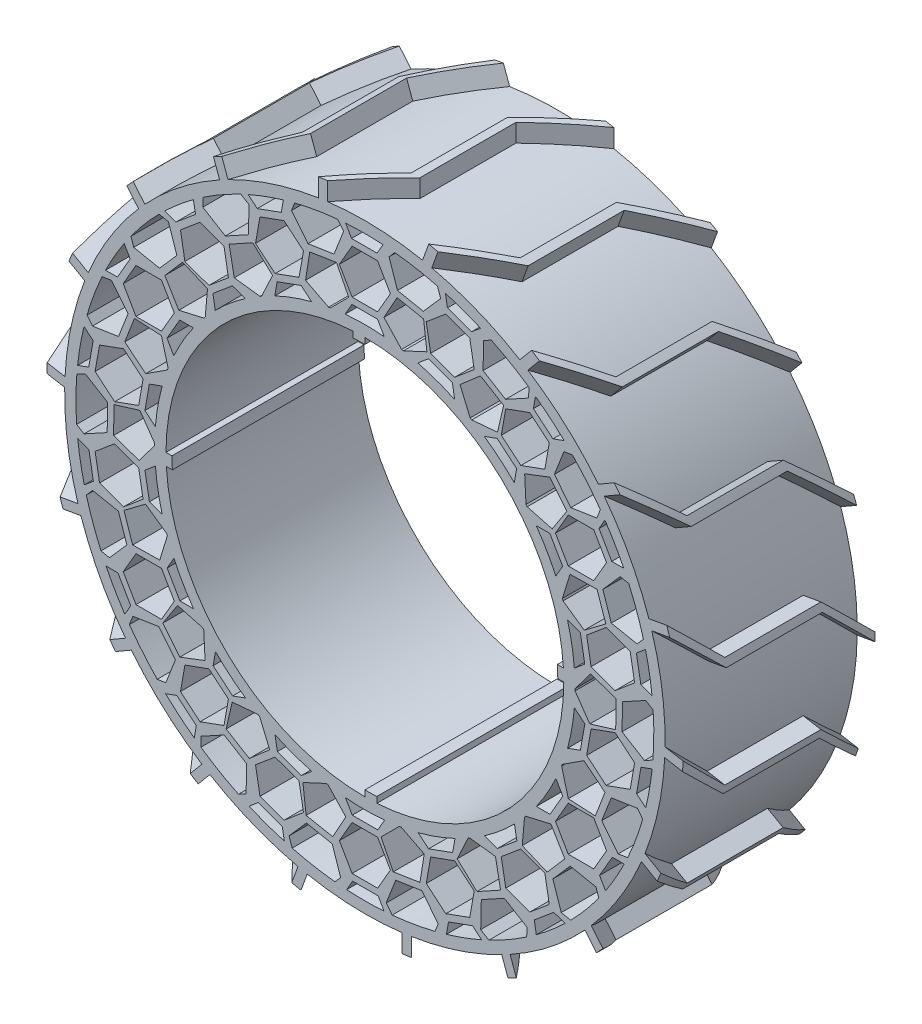
SolidWorks part; units mm, degrees
material "POLYURETHANE (11671)"
ref_plane "Front Plane" through (0, 0, 0) normal (0, 0, 1) x (1, 0, 0)
ref_plane "Top Plane" through (0, 0, 0) normal (0, 1, 0) x (1, 0, 0)
ref_plane "Right Plane" through (0, 0, 0) normal (1, 0, 0) x (0, 0, -1)
sketch "Sketch1" plane through (0, 0, 0) normal (0, 0, 1) x (1, 0, 0)
  line L0 (0, 120.3125) -> (0, 87.5) construction
  line L1 (5.083, 115.764) -> (7.5714, 120.074)
  line L2 (5.3125, 94.7047) -> (10.625, 103.9063)
  line L3 (10.625, 103.9063) -> (5.3125, 113.1078)
  line L4 (5.3125, 113.1078) -> (-5.3125, 113.1078)
  line L5 (-5.3125, 113.1078) -> (-10.625, 103.9062)
  line L6 (-10.625, 103.9062) -> (-5.3125, 94.7047)
  line L7 (-5.3125, 94.7047) -> (5.3125, 94.7047)
  line L12 (-5.542, 115.764) -> (5.083, 115.764)
  line L14 (8.0962, 87.1246) -> (5.2534, 92.0485)
  line L15 (5.2534, 92.0485) -> (-5.3716, 92.0485)
  line L16 (-5.3716, 92.0485) -> (-8.2212, 87.1129)
  line L19 (44.3701, 107.0441) -> (48.1825, 110.2431)
  line L20 (37.383, 87.1764) -> (45.5223, 94.006)
  line L21 (45.5223, 94.006) -> (43.6773, 104.4696)
  line L22 (43.6773, 104.4696) -> (33.693, 108.1035)
  line L23 (33.693, 108.1035) -> (25.5538, 101.2739)
  line L24 (25.5538, 101.2739) -> (27.3988, 90.8103)
  line L25 (27.3988, 90.8103) -> (37.383, 87.1764)
  line L27 (34.3859, 110.6781) -> (44.3701, 107.0441)
  line L28 (37.4063, 79.1013) -> (36.419, 84.7005)
  line L29 (36.419, 84.7005) -> (26.4348, 88.3345)
  line L30 (26.4348, 88.3345) -> (22.069, 84.6712)
  line L31 (41.1493, 113.0568) -> (29.9268, 82.2231) construction
  line L32 (78.3055, 85.4131) -> (82.9821, 87.1152)
  line L33 (64.9446, 69.1332) -> (74.9289, 72.7672)
  line L34 (74.9289, 72.7672) -> (76.7739, 83.2308)
  line L35 (76.7739, 83.2308) -> (68.6347, 90.0604)
  line L36 (68.6347, 90.0604) -> (58.6504, 86.4264)
  line L37 (58.6504, 86.4264) -> (56.8054, 75.9628)
  line L38 (56.8054, 75.9628) -> (64.9446, 69.1332)
  line L40 (70.1663, 92.2427) -> (78.3055, 85.4131)
  line L41 (62.2047, 61.5372) -> (63.192, 67.1364)
  line L42 (63.192, 67.1364) -> (55.0527, 73.966)
  line L43 (55.0527, 73.966) -> (49.6973, 72.0168)
  line L44 (77.3354, 92.1647) -> (56.2439, 67.0289) construction
  line L45 (102.7961, 53.48) -> (107.7729, 53.48)
  line L46 (84.673, 42.7516) -> (95.298, 42.7516)
  line L47 (95.298, 42.7516) -> (100.6105, 51.9531)
  line L48 (100.6105, 51.9531) -> (95.298, 61.1546)
  line L49 (95.298, 61.1546) -> (84.673, 61.1546)
  line L50 (84.673, 61.1546) -> (79.3605, 51.9531)
  line L51 (79.3605, 51.9531) -> (84.673, 42.7516)
  line L53 (97.4836, 62.6815) -> (102.7961, 53.48)
  line L54 (79.5002, 36.5508) -> (82.343, 41.4747)
  line L55 (82.343, 41.4747) -> (77.0305, 50.6762)
  line L56 (77.0305, 50.6762) -> (71.3314, 50.6762)
  line L57 (104.1937, 60.1563) -> (75.7772, 43.75) construction
  line L58 (114.888, 15.0964) -> (119.5646, 13.3942)
  line L59 (94.1885, 11.2135) -> (104.1727, 7.5795)
  line L60 (104.1727, 7.5795) -> (112.3119, 14.4092)
  line L61 (112.3119, 14.4092) -> (110.4669, 24.8727)
  line L62 (110.4669, 24.8727) -> (100.4827, 28.5067)
  line L63 (100.4827, 28.5067) -> (92.3434, 21.6771)
  line L64 (92.3434, 21.6771) -> (94.1885, 11.2135)
  line L66 (113.043, 25.56) -> (114.888, 15.0964)
  line L67 (87.2069, 7.1559) -> (91.5623, 10.8105)
  line L68 (91.5623, 10.8105) -> (89.7173, 21.2741)
  line L69 (89.7173, 21.2741) -> (84.3619, 23.2233)
  line L70 (118.4847, 20.892) -> (86.1707, 15.1942) construction
  line L71 (113.1226, -25.108) -> (116.9351, -28.307)
  line L72 (92.3434, -21.6771) -> (100.4827, -28.5067)
  line L73 (100.4827, -28.5067) -> (110.4669, -24.8727)
  line L74 (110.4669, -24.8727) -> (112.3119, -14.4092)
  line L75 (112.3119, -14.4092) -> (104.1727, -7.5795)
  line L76 (104.1727, -7.5795) -> (94.1885, -11.2135)
  line L77 (94.1885, -11.2135) -> (92.3434, -21.6771)
  line L79 (114.9677, -14.6444) -> (113.1226, -25.108)
  line L80 (84.3951, -23.1022) -> (89.7378, -21.1576)
  line L81 (89.7378, -21.1576) -> (91.5828, -10.694)
  line L82 (91.5828, -10.694) -> (87.2171, -7.0307)
  line L83 (118.4847, -20.892) -> (86.1707, -15.1942) construction
  line L84 (97.7131, -62.284) -> (100.2014, -66.594)
  line L85 (79.3605, -51.9531) -> (84.673, -61.1546)
  line L86 (84.673, -61.1546) -> (95.298, -61.1546)
  line L87 (95.298, -61.1546) -> (100.6105, -51.9531)
  line L88 (100.6105, -51.9531) -> (95.298, -42.7516)
  line L89 (95.298, -42.7516) -> (84.673, -42.7516)
  line L90 (84.673, -42.7516) -> (79.3605, -51.9531)
  line L92 (103.0256, -53.0825) -> (97.7131, -62.284)
  line L93 (71.4041, -50.5738) -> (77.0896, -50.5738)
  line L94 (77.0896, -50.5738) -> (82.4021, -41.3723)
  line L95 (82.4021, -41.3723) -> (79.5526, -36.4367)
  line L96 (104.1937, -60.1563) -> (75.7772, -43.75) construction
  line L97 (70.5178, -91.9477) -> (71.3821, -96.8489)
  line L98 (56.8054, -75.9628) -> (58.6504, -86.4264)
  line L99 (58.6504, -86.4264) -> (68.6347, -90.0604)
  line L100 (68.6347, -90.0604) -> (76.7739, -83.2308)
  line L101 (76.7739, -83.2308) -> (74.9289, -72.7672)
  line L102 (74.9289, -72.7672) -> (64.9446, -69.1332)
  line L103 (64.9446, -69.1332) -> (56.8054, -75.9628)
  line L105 (78.6571, -85.1181) -> (70.5178, -91.9477)
  line L106 (49.8006, -71.9455) -> (55.1433, -73.89)
  line L107 (55.1433, -73.89) -> (63.2825, -67.0604)
  line L108 (63.2825, -67.0604) -> (62.2929, -61.4479)
  line L109 (77.3354, -92.1647) -> (56.2439, -67.0289) construction
  line L110 (34.8171, -110.5211) -> (33.9529, -115.4223)
  line L111 (27.3988, -90.8103) -> (25.5538, -101.2739)
  line L112 (25.5538, -101.2739) -> (33.693, -108.1035)
  line L113 (33.693, -108.1035) -> (43.6773, -104.4696)
  line L114 (43.6773, -104.4696) -> (45.5223, -94.006)
  line L115 (45.5223, -94.006) -> (37.383, -87.1764)
  line L116 (37.383, -87.1764) -> (27.3988, -90.8103)
  line L118 (44.8014, -106.8871) -> (34.8171, -110.5211)
  line L119 (22.1905, -84.6394) -> (26.5459, -88.294)
  line L120 (26.5459, -88.294) -> (36.5301, -84.6601)
  line L121 (36.5301, -84.6601) -> (37.5197, -79.0476)
  line L122 (41.1493, -113.0568) -> (29.9268, -82.2231) construction
  line L123 (-5.083, -115.764) -> (-7.5714, -120.074)
  line L124 (-5.3125, -94.7047) -> (-10.625, -103.9063)
  line L125 (-10.625, -103.9063) -> (-5.3125, -113.1078)
  line L126 (-5.3125, -113.1078) -> (5.3125, -113.1078)
  line L127 (5.3125, -113.1078) -> (10.625, -103.9063)
  line L128 (10.625, -103.9063) -> (5.3125, -94.7047)
  line L129 (5.3125, -94.7047) -> (-5.3125, -94.7047)
  line L131 (5.542, -115.764) -> (-5.083, -115.764)
  line L132 (-8.0962, -87.1246) -> (-5.2534, -92.0485)
  line L133 (-5.2534, -92.0485) -> (5.3716, -92.0485)
  line L134 (5.3716, -92.0485) -> (8.2212, -87.1129)
  line L135 (0, -120.3125) -> (0, -87.5) construction
  line L136 (-44.3701, -107.0441) -> (-48.1825, -110.2431)
  line L137 (-37.383, -87.1764) -> (-45.5223, -94.006)
  line L138 (-45.5223, -94.006) -> (-43.6773, -104.4696)
  line L139 (-43.6773, -104.4696) -> (-33.693, -108.1035)
  line L140 (-33.693, -108.1035) -> (-25.5538, -101.2739)
  line L141 (-25.5538, -101.2739) -> (-27.3988, -90.8103)
  line L142 (-27.3988, -90.8103) -> (-37.383, -87.1764)
  line L144 (-34.3859, -110.6781) -> (-44.3701, -107.0441)
  line L145 (-37.4063, -79.1013) -> (-36.419, -84.7005)
  line L146 (-36.419, -84.7005) -> (-26.4348, -88.3345)
  line L147 (-26.4348, -88.3345) -> (-22.069, -84.6712)
  line L148 (-41.1493, -113.0568) -> (-29.9268, -82.2231) construction
  line L149 (-78.3055, -85.4131) -> (-82.9821, -87.1152)
  line L150 (-64.9446, -69.1332) -> (-74.9289, -72.7672)
  line L151 (-74.9289, -72.7672) -> (-76.7739, -83.2308)
  line L152 (-76.7739, -83.2308) -> (-68.6347, -90.0604)
  line L153 (-68.6347, -90.0604) -> (-58.6504, -86.4264)
  line L154 (-58.6504, -86.4264) -> (-56.8054, -75.9628)
  line L155 (-56.8054, -75.9628) -> (-64.9446, -69.1332)
  line L157 (-70.1663, -92.2427) -> (-78.3055, -85.4131)
  line L158 (-62.2047, -61.5372) -> (-63.192, -67.1364)
  line L159 (-63.192, -67.1364) -> (-55.0527, -73.966)
  line L160 (-55.0527, -73.966) -> (-49.6973, -72.0168)
  line L161 (-77.3354, -92.1647) -> (-56.2439, -67.0289) construction
  line L162 (-102.7961, -53.48) -> (-107.7729, -53.48)
  line L163 (-84.673, -42.7516) -> (-95.298, -42.7516)
  line L164 (-95.298, -42.7516) -> (-100.6105, -51.9531)
  line L165 (-100.6105, -51.9531) -> (-95.298, -61.1546)
  line L166 (-95.298, -61.1546) -> (-84.673, -61.1546)
  line L167 (-84.673, -61.1546) -> (-79.3605, -51.9531)
  line L168 (-79.3605, -51.9531) -> (-84.673, -42.7516)
  line L170 (-97.4836, -62.6815) -> (-102.7961, -53.48)
  line L171 (-79.5002, -36.5508) -> (-82.343, -41.4747)
  line L172 (-82.343, -41.4747) -> (-77.0305, -50.6762)
  line L173 (-77.0305, -50.6762) -> (-71.3314, -50.6762)
  line L174 (-104.1937, -60.1563) -> (-75.7772, -43.75) construction
  line L175 (-114.888, -15.0964) -> (-119.5646, -13.3942)
  line L176 (-94.1885, -11.2135) -> (-104.1727, -7.5795)
  line L177 (-104.1727, -7.5795) -> (-112.3119, -14.4092)
  line L178 (-112.3119, -14.4092) -> (-110.4669, -24.8727)
  line L179 (-110.4669, -24.8727) -> (-100.4827, -28.5067)
  line L180 (-100.4827, -28.5067) -> (-92.3434, -21.6771)
  line L181 (-92.3434, -21.6771) -> (-94.1885, -11.2135)
  line L183 (-113.043, -25.56) -> (-114.888, -15.0964)
  line L184 (-87.2069, -7.1559) -> (-91.5623, -10.8105)
  line L185 (-91.5623, -10.8105) -> (-89.7173, -21.2741)
  line L186 (-89.7173, -21.2741) -> (-84.3619, -23.2233)
  line L187 (-118.4847, -20.892) -> (-86.1707, -15.1942) construction
  line L188 (-113.1226, 25.108) -> (-116.9351, 28.307)
  line L189 (-92.3434, 21.6771) -> (-100.4827, 28.5067)
  line L190 (-100.4827, 28.5067) -> (-110.4669, 24.8727)
  line L191 (-110.4669, 24.8727) -> (-112.3119, 14.4092)
  line L192 (-112.3119, 14.4092) -> (-104.1727, 7.5795)
  line L193 (-104.1727, 7.5795) -> (-94.1885, 11.2135)
  line L194 (-94.1885, 11.2135) -> (-92.3434, 21.6771)
  line L196 (-114.9677, 14.6444) -> (-113.1226, 25.108)
  line L197 (-84.3951, 23.1022) -> (-89.7378, 21.1576)
  line L198 (-89.7378, 21.1576) -> (-91.5828, 10.694)
  line L199 (-91.5828, 10.694) -> (-87.2171, 7.0307)
  line L200 (-118.4847, 20.892) -> (-86.1707, 15.1942) construction
  line L201 (-97.7131, 62.284) -> (-100.2014, 66.594)
  line L202 (-79.3605, 51.9531) -> (-84.673, 61.1546)
  line L203 (-84.673, 61.1546) -> (-95.298, 61.1546)
  line L204 (-95.298, 61.1546) -> (-100.6105, 51.9531)
  line L205 (-100.6105, 51.9531) -> (-95.298, 42.7516)
  line L206 (-95.298, 42.7516) -> (-84.673, 42.7516)
  line L207 (-84.673, 42.7516) -> (-79.3605, 51.9531)
  line L209 (-103.0256, 53.0825) -> (-97.7131, 62.284)
  line L210 (-71.4041, 50.5738) -> (-77.0896, 50.5738)
  line L211 (-77.0896, 50.5738) -> (-82.4021, 41.3723)
  line L212 (-82.4021, 41.3723) -> (-79.5526, 36.4367)
  line L213 (-104.1937, 60.1562) -> (-75.7772, 43.75) construction
  line L214 (-70.5178, 91.9477) -> (-71.3821, 96.8489)
  line L215 (-56.8054, 75.9628) -> (-58.6504, 86.4264)
  line L216 (-58.6504, 86.4264) -> (-68.6347, 90.0604)
  line L217 (-68.6347, 90.0604) -> (-76.7739, 83.2308)
  line L218 (-76.7739, 83.2308) -> (-74.9289, 72.7672)
  line L219 (-74.9289, 72.7672) -> (-64.9446, 69.1332)
  line L220 (-64.9446, 69.1332) -> (-56.8054, 75.9628)
  line L222 (-78.6571, 85.1181) -> (-70.5178, 91.9477)
  line L223 (-49.8006, 71.9455) -> (-55.1433, 73.89)
  line L224 (-55.1433, 73.89) -> (-63.2825, 67.0604)
  line L225 (-63.2825, 67.0604) -> (-62.2929, 61.4479)
  line L226 (-77.3354, 92.1647) -> (-56.2439, 67.0289) construction
  line L227 (-34.8171, 110.5211) -> (-33.9529, 115.4223)
  line L228 (-27.3988, 90.8103) -> (-25.5538, 101.2739)
  line L229 (-25.5538, 101.2739) -> (-33.693, 108.1035)
  line L230 (-33.693, 108.1035) -> (-43.6773, 104.4696)
  line L231 (-43.6773, 104.4696) -> (-45.5223, 94.006)
  line L232 (-45.5223, 94.006) -> (-37.383, 87.1764)
  line L233 (-37.383, 87.1764) -> (-27.3988, 90.8103)
  line L235 (-44.8014, 106.8871) -> (-34.8171, 110.5211)
  line L236 (-22.1905, 84.6394) -> (-26.5459, 88.294)
  line L237 (-26.5459, 88.294) -> (-36.5301, 84.6601)
  line L238 (-36.5301, 84.6601) -> (-37.5197, 79.0476)
  line L239 (-41.1493, 113.0568) -> (-29.9268, 82.2231) construction
  line L240 (-25.5538, 101.2739) -> (-10.625, 103.9062) construction
  line L247 (-25.5538, 101.2739) -> (-6.7964, 89.5807) construction
  line L248 (-6.7964, 89.5807) -> (-10.625, 103.9062) construction
  line L249 (-10.625, 103.9062) -> (-22.9692, 85.2929) construction
  line L251 (-14.7311, 86.2511) -> (-17.7031, 103.9865) construction
  line L252 (-17.7031, 103.9865) -> (-26.9388, 90.0604) construction
  line L253 (-26.9388, 90.0604) -> (-7.9687, 99.3055) construction
  line L254 (-7.9687, 99.3055) -> (-5.3716, 93.9764) construction
  line L255 (-5.3716, 93.9764) -> (-26.4763, 96.0421) construction
  line L257 (-14.3347, 86.3178) -> (-6.7191, 93.9229)
  line L258 (-6.7191, 93.9229) -> (-11.8222, 103.9556)
  line L259 (-11.8222, 103.9556) -> (-22.9409, 102.2025)
  line L260 (-22.9409, 102.2025) -> (-24.7095, 91.0863)
  line L261 (-24.7095, 91.0863) -> (-15.1082, 86.1858)
  line L262 (-8.8671, 116.6558) -> (-11.3652, 119.7745)
  line L265 (-30.5411, 113.3409) -> (-23.6873, 104.7845)
  line L266 (-23.6873, 104.7845) -> (-12.8502, 106.4419)
  line L267 (-12.8502, 106.4419) -> (-8.8671, 116.6558)
  line L269 (31.5663, 112.6533) -> (30.2854, 116.4383)
  line L270 (24.33, 104.4177) -> (31.5663, 112.6533)
  line L271 (13.5797, 106.5667) -> (24.33, 104.4177)
  line L272 (10.0656, 116.9513) -> (13.5797, 106.5667)
  line L273 (16.0522, 86.015) -> (25.8096, 90.5567)
  line L274 (25.8096, 90.5567) -> (24.4457, 101.7297)
  line L275 (24.4457, 101.7297) -> (13.398, 103.8852)
  line L276 (13.398, 103.8852) -> (7.9341, 94.0443)
  line L277 (7.9341, 94.0443) -> (15.2802, 86.1555)
  line L280 (68.1923, 95.0632) -> (68.2833, 99.058)
  line L281 (58.5757, 89.7992) -> (68.1923, 95.0632)
  line L282 (49.2087, 95.4955) -> (58.5757, 89.7992)
  line L283 (49.4583, 106.4557) -> (49.2087, 95.4955)
  line L284 (44.503, 75.3375) -> (55.2253, 76.268)
  line L285 (55.2253, 76.268) -> (57.765, 87.2338)
  line L286 (57.765, 87.2338) -> (48.1208, 93.0378)
  line L287 (48.1208, 93.0378) -> (39.6206, 85.6591)
  line L288 (39.6206, 85.6591) -> (43.8256, 75.7335)
  line L291 (96.5933, 66.007) -> (98.0451, 69.7298)
  line L292 (85.7563, 64.3496) -> (96.5933, 66.007)
  line L293 (78.9024, 72.906) -> (85.7563, 64.3496)
  line L294 (82.8856, 83.1199) -> (78.9024, 72.906)
  line L295 (67.5861, 55.5732) -> (77.98, 52.7803)
  line L296 (77.98, 52.7803) -> (84.1171, 62.2161)
  line L297 (84.1171, 62.2161) -> (77.0396, 70.9686)
  line L298 (77.0396, 70.9686) -> (66.5283, 66.9422)
  line L299 (66.5283, 66.9422) -> (67.085, 56.177)
  line L302 (113.3438, 28.9894) -> (115.9813, 31.9912)
  line L303 (102.5934, 31.1385) -> (113.3438, 28.9894)
  line L304 (99.0793, 41.523) -> (102.5934, 31.1385)
  line L305 (106.3156, 49.7586) -> (99.0793, 41.523)
  line L306 (82.5173, 29.1059) -> (91.3292, 22.9265)
  line L307 (91.3292, 22.9265) -> (100.3234, 29.6943)
  line L308 (100.3234, 29.6943) -> (96.6662, 40.3396)
  line L309 (96.6662, 40.3396) -> (85.4118, 40.151)
  line L310 (85.4118, 40.151) -> (82.2529, 29.8447)
  line L313 (116.4233, -11.5247) -> (119.9284, -9.606)
  line L314 (107.0563, -5.8284) -> (116.4233, -11.5247)
  line L315 (107.3058, 5.1318) -> (107.0563, -5.8284)
  line L316 (116.9224, 10.3957) -> (107.3058, 5.1318)
  line L317 (87.4957, -0.872) -> (93.6627, -9.6925)
  line L318 (93.6627, -9.6925) -> (104.4292, -6.4091)
  line L319 (104.4292, -6.4091) -> (104.6335, 4.8451)
  line L320 (104.6335, 4.8451) -> (93.9933, 8.5171)
  line L321 (93.9933, 8.5171) -> (87.5, -0.0873)
  line L324 (105.4604, -50.6488) -> (109.4104, -50.0447)
  line L325 (98.6065, -42.0923) -> (105.4604, -50.6488)
  line L326 (102.5897, -31.8785) -> (98.6065, -42.0923)
  line L327 (113.4267, -30.2211) -> (102.5897, -31.8785)
  line L328 (81.9208, -30.7447) -> (84.6991, -41.1425)
  line L329 (84.6991, -41.1425) -> (95.9393, -41.7395)
  line L330 (95.9393, -41.7395) -> (99.9804, -31.2339)
  line L331 (99.9804, -31.2339) -> (91.2378, -24.1441)
  line L332 (91.2378, -24.1441) -> (82.1932, -30.0088)
  line L335 (81.7775, -83.6639) -> (85.6958, -84.4471)
  line L336 (78.2634, -73.2793) -> (81.7775, -83.6639)
  line L337 (85.4997, -65.0437) -> (78.2634, -73.2793)
  line L338 (96.25, -67.1927) -> (85.4997, -65.0437)
  line L339 (66.4651, -56.9091) -> (65.5196, -67.6301)
  line L340 (65.5196, -67.6301) -> (75.8777, -72.0354)
  line L341 (75.8777, -72.0354) -> (83.2682, -63.5456)
  line L342 (83.2682, -63.5456) -> (77.4777, -53.8932)
  line L343 (77.4777, -53.8932) -> (66.9727, -56.3108)
  line L346 (48.231, -106.5879) -> (51.6451, -108.6641)
  line L347 (48.4806, -95.6277) -> (48.231, -106.5879)
  line L348 (58.0972, -90.3637) -> (48.4806, -95.6277)
  line L349 (67.4642, -96.06) -> (58.0972, -90.3637)
  line L350 (42.9927, -76.2094) -> (38.4374, -85.9606)
  line L351 (38.4374, -85.9606) -> (46.6641, -93.6429)
  line L352 (46.6641, -93.6429) -> (56.5127, -88.1927)
  line L353 (56.5127, -88.1927) -> (54.3727, -77.142)
  line L354 (54.3727, -77.142) -> (43.6743, -75.8208)
  line L357 (8.8671, -116.6558) -> (11.3652, -119.7745)
  line L358 (12.8502, -106.4419) -> (8.8671, -116.6558)
  line L359 (23.6873, -104.7845) -> (12.8502, -106.4419)
  line L360 (30.5411, -113.3409) -> (23.6873, -104.7845)
  line L361 (14.3347, -86.3178) -> (6.7191, -93.9229)
  line L362 (6.7191, -93.9229) -> (11.8222, -103.9556)
  line L363 (11.8222, -103.9556) -> (22.9409, -102.2025)
  line L364 (22.9409, -102.2025) -> (24.7095, -91.0863)
  line L365 (24.7095, -91.0863) -> (15.1082, -86.1858)
  line L368 (-31.5663, -112.6533) -> (-30.2854, -116.4383)
  line L369 (-24.33, -104.4177) -> (-31.5663, -112.6533)
  line L370 (-13.5797, -106.5667) -> (-24.33, -104.4177)
  line L371 (-10.0656, -116.9513) -> (-13.5797, -106.5667)
  line L372 (-16.0522, -86.015) -> (-25.8096, -90.5567)
  line L373 (-25.8096, -90.5567) -> (-24.4457, -101.7297)
  line L374 (-24.4457, -101.7297) -> (-13.398, -103.8852)
  line L375 (-13.398, -103.8852) -> (-7.9341, -94.0443)
  line L376 (-7.9341, -94.0443) -> (-15.2802, -86.1555)
  line L379 (-68.1923, -95.0632) -> (-68.2833, -99.058)
  line L380 (-58.5757, -89.7992) -> (-68.1923, -95.0632)
  line L381 (-49.2087, -95.4955) -> (-58.5757, -89.7992)
  line L382 (-49.4583, -106.4557) -> (-49.2087, -95.4955)
  line L383 (-44.503, -75.3375) -> (-55.2253, -76.268)
  line L384 (-55.2253, -76.268) -> (-57.765, -87.2338)
  line L385 (-57.765, -87.2338) -> (-48.1208, -93.0378)
  line L386 (-48.1208, -93.0378) -> (-39.6206, -85.6591)
  line L387 (-39.6206, -85.6591) -> (-43.8256, -75.7335)
  line L390 (-96.5933, -66.007) -> (-98.0451, -69.7298)
  line L391 (-85.7563, -64.3496) -> (-96.5933, -66.007)
  line L392 (-78.9024, -72.906) -> (-85.7563, -64.3496)
  line L393 (-82.8856, -83.1199) -> (-78.9024, -72.906)
  line L394 (-67.5861, -55.5732) -> (-77.98, -52.7803)
  line L395 (-77.98, -52.7803) -> (-84.1171, -62.2161)
  line L396 (-84.1171, -62.2161) -> (-77.0396, -70.9686)
  line L397 (-77.0396, -70.9686) -> (-66.5283, -66.9422)
  line L398 (-66.5283, -66.9422) -> (-67.085, -56.177)
  line L401 (-113.3438, -28.9894) -> (-115.9813, -31.9912)
  line L402 (-102.5934, -31.1385) -> (-113.3438, -28.9894)
  line L403 (-99.0793, -41.523) -> (-102.5934, -31.1385)
  line L404 (-106.3156, -49.7586) -> (-99.0793, -41.523)
  line L405 (-82.5173, -29.1059) -> (-91.3292, -22.9265)
  line L406 (-91.3292, -22.9265) -> (-100.3234, -29.6943)
  line L407 (-100.3234, -29.6943) -> (-96.6662, -40.3396)
  line L408 (-96.6662, -40.3396) -> (-85.4118, -40.151)
  line L409 (-85.4118, -40.151) -> (-82.2529, -29.8447)
  line L412 (-116.4233, 11.5247) -> (-119.9284, 9.606)
  line L413 (-107.0563, 5.8284) -> (-116.4233, 11.5247)
  line L414 (-107.3058, -5.1318) -> (-107.0563, 5.8284)
  line L415 (-116.9224, -10.3957) -> (-107.3058, -5.1318)
  line L416 (-87.4957, 0.872) -> (-93.6627, 9.6925)
  line L417 (-93.6627, 9.6925) -> (-104.4292, 6.4091)
  line L418 (-104.4292, 6.4091) -> (-104.6335, -4.8451)
  line L419 (-104.6335, -4.8451) -> (-93.9933, -8.5171)
  line L420 (-93.9933, -8.5171) -> (-87.5, 0.0873)
  line L423 (-105.4604, 50.6488) -> (-109.4104, 50.0447)
  line L424 (-98.6065, 42.0923) -> (-105.4604, 50.6488)
  line L425 (-102.5897, 31.8785) -> (-98.6065, 42.0923)
  line L426 (-113.4267, 30.2211) -> (-102.5897, 31.8785)
  line L427 (-81.9208, 30.7447) -> (-84.6991, 41.1425)
  line L428 (-84.6991, 41.1425) -> (-95.9393, 41.7395)
  line L429 (-95.9393, 41.7395) -> (-99.9804, 31.2339)
  line L430 (-99.9804, 31.2339) -> (-91.2378, 24.1441)
  line L431 (-91.2378, 24.1441) -> (-82.1932, 30.0088)
  line L434 (-81.7775, 83.6639) -> (-85.6958, 84.4471)
  line L435 (-78.2634, 73.2793) -> (-81.7775, 83.6639)
  line L436 (-85.4997, 65.0437) -> (-78.2634, 73.2793)
  line L437 (-96.25, 67.1927) -> (-85.4997, 65.0437)
  line L438 (-66.4651, 56.9091) -> (-65.5196, 67.6301)
  line L439 (-65.5196, 67.6301) -> (-75.8777, 72.0354)
  line L440 (-75.8777, 72.0354) -> (-83.2682, 63.5456)
  line L441 (-83.2682, 63.5456) -> (-77.4777, 53.8932)
  line L442 (-77.4777, 53.8932) -> (-66.9727, 56.3108)
  line L445 (-48.231, 106.5879) -> (-51.6451, 108.6641)
  line L446 (-48.4806, 95.6277) -> (-48.231, 106.5879)
  line L447 (-58.0972, 90.3637) -> (-48.4806, 95.6277)
  line L448 (-67.4642, 96.06) -> (-58.0972, 90.3637)
  line L449 (-42.9927, 76.2094) -> (-38.4374, 85.9606)
  line L450 (-38.4374, 85.9606) -> (-46.6641, 93.6429)
  line L451 (-46.6641, 93.6429) -> (-56.5127, 88.1927)
  line L452 (-56.5127, 88.1927) -> (-54.3727, 77.142)
  line L453 (-54.3727, 77.142) -> (-43.6743, 75.8208)
  line L455 (-29.228, 116.7083) -> (-30.5411, 113.3409)
  line L457 (-8.0138, 120.0453) -> (-5.542, 115.764)
  line L459 (12.4513, 119.6665) -> (10.0656, 116.9513)
  line L461 (33.5274, 115.5466) -> (34.3859, 110.6781)
  line L463 (52.6287, 108.1911) -> (49.4583, 106.4557)
  line L465 (71.0247, 97.1112) -> (70.1663, 92.2427)
  line L467 (86.4584, 83.6663) -> (82.8856, 83.1199)
  line L469 (99.9554, 66.9628) -> (97.4836, 62.6815)
  line L471 (109.8598, 49.0501) -> (106.3156, 49.7586)
  line L473 (116.83, 28.7377) -> (113.043, 25.56)
  line L475 (120.0106, 8.5177) -> (116.9224, 10.3957)
  line L477 (119.6131, -12.9536) -> (114.9677, -14.6444)
  line L479 (115.6863, -33.042) -> (113.4267, -30.2211)
  line L481 (107.9692, -53.0825) -> (103.0256, -53.0825)
  line L483 (97.4086, -70.6164) -> (96.25, -67.1927)
  line L485 (83.3025, -86.8089) -> (78.6571, -85.1181)
  line L487 (67.3819, -99.6734) -> (67.4642, -96.06)
  line L488 (-86.4584, -83.6663) -> (-82.8856, -83.1199)
  line L489 (48.5884, -110.0648) -> (44.8014, -106.8871)
  line L491 (29.228, -116.7083) -> (30.5411, -113.3409)
  line L492 (-52.6287, -108.1911) -> (-49.4583, -106.4557)
  line L493 (8.0138, -120.0453) -> (5.542, -115.764)
  line L495 (-12.4513, -119.6665) -> (-10.0656, -116.9513)
  line L496 (-71.0247, -97.1112) -> (-70.1663, -92.2427)
  line L497 (-33.5274, -115.5466) -> (-34.3859, -110.6781)
  line L508 (-99.9554, -66.9628) -> (-97.4836, -62.6815)
  line L510 (-109.8598, -49.0501) -> (-106.3156, -49.7586)
  line L512 (-116.83, -28.7377) -> (-113.043, -25.56)
  line L514 (-120.0106, -8.5177) -> (-116.9224, -10.3957)
  line L516 (-119.6131, 12.9536) -> (-114.9677, 14.6444)
  line L518 (-115.6863, 33.042) -> (-113.4267, 30.2211)
  line L520 (-107.9692, 53.0825) -> (-103.0256, 53.0825)
  line L522 (-97.4086, 70.6164) -> (-96.25, 67.1927)
  line L524 (-83.3025, 86.8089) -> (-78.6571, 85.1181)
  line L526 (-67.3819, 99.6734) -> (-67.4642, 96.06)
  line L528 (-48.5884, 110.0648) -> (-44.8014, 106.8871)
  arc A2 (-11.3652, 119.7745) -> (-29.228, 116.7083) centre (0, 0) ccw
  arc A3 (-22.1905, 84.6394) -> (-37.5197, 79.0476) centre (0, 0) ccw
  circle A4 centre (0, 103.9062) radius 9.2015 construction
  circle A5 centre (35.538, 97.6399) radius 9.2015 construction
  circle A6 centre (66.7897, 79.5968) radius 9.2015 construction
  circle A7 centre (89.9855, 51.9531) radius 9.2015 construction
  circle A8 centre (102.3277, 18.0431) radius 9.2015 construction
  circle A9 centre (102.3277, -18.0431) radius 9.2015 construction
  circle A10 centre (89.9855, -51.9531) radius 9.2015 construction
  circle A11 centre (66.7897, -79.5968) radius 9.2015 construction
  circle A12 centre (35.538, -97.6399) radius 9.2015 construction
  circle A13 centre (0, -103.9063) radius 9.2015 construction
  circle A14 centre (-35.538, -97.6399) radius 9.2015 construction
  circle A15 centre (-66.7897, -79.5968) radius 9.2015 construction
  circle A16 centre (-89.9855, -51.9531) radius 9.2015 construction
  circle A17 centre (-102.3277, -18.0431) radius 9.2015 construction
  circle A18 centre (-102.3277, 18.0431) radius 9.2015 construction
  circle A19 centre (-89.9855, 51.9531) radius 9.2015 construction
  circle A20 centre (-66.7897, 79.5968) radius 9.2015 construction
  circle A21 centre (-35.538, 97.6399) radius 9.2015 construction
  circle A22 centre (0, 0) radius 82.8125
  circle A23 centre (-16.1751, 95.4273) radius 7.7463 construction
  arc A24 (12.6499, 119.6456) -> (30.1625, 116.4702) centre (20.8159, 114.8023) ccw construction
  circle A25 centre (17.4384, 95.2045) radius 7.7463 construction
  arc A26 (52.8083, 108.1036) -> (68.1787, 99.13) centre (58.8253, 100.7594) ccw construction
  circle A27 centre (48.9487, 83.4987) radius 7.7463 construction
  arc A28 (86.5972, 83.5226) -> (97.9715, 69.8333) centre (89.7394, 74.5634) ccw construction
  circle A29 centre (74.5549, 61.7217) radius 7.7463 construction
  arc A30 (109.9411, 48.8676) -> (115.9475, 32.1136) centre (109.8297, 39.374) ccw construction
  circle A31 centre (91.1688, 32.5001) radius 7.7463 construction
  arc A32 (120.0246, 8.3185) -> (119.9385, -9.4795) centre (116.6729, -0.5645) ccw construction
  circle A33 centre (96.7863, -0.6414) radius 7.7463 construction
  arc A34 (115.6313, -33.234) -> (109.4631, -49.9292) centre (109.4436, -40.4349) ccw construction
  circle A35 centre (90.73, -33.7056) radius 7.7463 construction
  arc A36 (97.2912, -70.778) -> (85.7849, -84.3567) centre (89.0138, -75.4283) ccw construction
  circle A37 centre (73.7303, -62.7044) radius 7.7463 construction
  arc A38 (67.2163, -99.7851) -> (51.7598, -108.6095) centre (57.8476, -101.3239) ccw construction
  circle A39 centre (47.8377, -84.1401) radius 7.7463 construction
  arc A40 (29.0342, -116.7567) -> (11.4916, -119.7624) centre (19.7041, -114.9984) ccw construction
  circle A41 centre (16.1751, -95.4273) radius 7.7463 construction
  arc A42 (-12.6499, -119.6456) -> (-30.1625, -116.4702) centre (-20.8159, -114.8023) ccw construction
  circle A43 centre (-17.4384, -95.2045) radius 7.7463 construction
  arc A44 (-52.8083, -108.1036) -> (-68.1787, -99.13) centre (-58.8253, -100.7594) ccw construction
  circle A45 centre (-48.9487, -83.4987) radius 7.7463 construction
  arc A46 (-86.5972, -83.5226) -> (-97.9715, -69.8333) centre (-89.7394, -74.5634) ccw construction
  circle A47 centre (-74.5549, -61.7217) radius 7.7463 construction
  arc A48 (-109.9411, -48.8676) -> (-115.9475, -32.1136) centre (-109.8297, -39.374) ccw construction
  circle A49 centre (-91.1688, -32.5001) radius 7.7463 construction
  arc A50 (-120.0246, -8.3185) -> (-119.9385, 9.4795) centre (-116.6729, 0.5645) ccw construction
  circle A51 centre (-96.7863, 0.6414) radius 7.7463 construction
  arc A52 (-115.6313, 33.234) -> (-109.4631, 49.9292) centre (-109.4436, 40.4349) ccw construction
  circle A53 centre (-90.73, 33.7056) radius 7.7463 construction
  arc A54 (-97.2912, 70.778) -> (-85.7849, 84.3567) centre (-89.0138, 75.4283) ccw construction
  circle A55 centre (-73.7303, 62.7044) radius 7.7463 construction
  arc A56 (-67.2163, 99.7851) -> (-51.7598, 108.6095) centre (-57.8476, 101.3239) ccw construction
  circle A57 centre (-47.8377, 84.1401) radius 7.7463 construction
  arc A58 (7.5714, 120.074) -> (-8.0138, 120.0453) centre (0, 0) ccw
  arc A59 (30.2854, 116.4383) -> (12.4513, 119.6665) centre (0, 0) ccw
  arc A60 (48.1825, 110.2431) -> (33.5274, 115.5466) centre (0, 0) ccw
  arc A61 (68.2833, 99.058) -> (52.6287, 108.1911) centre (0, 0) ccw
  arc A62 (82.9821, 87.1152) -> (71.0247, 97.1112) centre (0, 0) ccw
  arc A63 (98.0451, 69.7298) -> (86.4584, 83.6663) centre (0, 0) ccw
  arc A64 (107.7729, 53.48) -> (99.9554, 66.9628) centre (0, 0) ccw
  arc A65 (115.9813, 31.9912) -> (109.8598, 49.0501) centre (0, 0) ccw
  arc A66 (119.5646, 13.3942) -> (116.83, 28.7377) centre (0, 0) ccw
  arc A67 (119.9284, -9.606) -> (120.0106, 8.5177) centre (0, 0) ccw
  arc A68 (116.9351, -28.307) -> (119.6131, -12.9536) centre (0, 0) ccw
  arc A69 (109.4104, -50.0447) -> (115.6863, -33.042) centre (0, 0) ccw
  arc A70 (100.2014, -66.594) -> (107.9692, -53.0825) centre (0, 0) ccw
  arc A71 (85.6958, -84.4471) -> (97.4086, -70.6164) centre (0, 0) ccw
  arc A72 (71.3821, -96.8489) -> (83.3025, -86.8089) centre (0, 0) ccw
  arc A73 (51.6451, -108.6641) -> (67.3819, -99.6734) centre (0, 0) ccw
  arc A74 (33.9529, -115.4223) -> (48.5884, -110.0648) centre (0, 0) ccw
  arc A75 (11.3652, -119.7745) -> (29.228, -116.7083) centre (0, 0) ccw
  arc A76 (-7.5714, -120.074) -> (8.0138, -120.0453) centre (0, 0) ccw
  arc A77 (-30.2854, -116.4383) -> (-12.4513, -119.6665) centre (0, 0) ccw
  arc A78 (-48.1825, -110.2431) -> (-33.5274, -115.5466) centre (0, 0) ccw
  arc A79 (-68.2833, -99.058) -> (-52.6287, -108.1911) centre (0, 0) ccw
  arc A80 (-82.9821, -87.1152) -> (-71.0247, -97.1112) centre (0, 0) ccw
  arc A81 (-98.0451, -69.7298) -> (-86.4584, -83.6663) centre (0, 0) ccw
  arc A82 (-107.7729, -53.48) -> (-99.9554, -66.9628) centre (0, 0) ccw
  arc A83 (-115.9813, -31.9912) -> (-109.8598, -49.0501) centre (0, 0) ccw
  arc A84 (-119.5646, -13.3942) -> (-116.83, -28.7377) centre (0, 0) ccw
  arc A85 (-119.9284, 9.606) -> (-120.0106, -8.5177) centre (0, 0) ccw
  arc A86 (-116.9351, 28.307) -> (-119.6131, 12.9536) centre (0, 0) ccw
  arc A87 (-109.4104, 50.0447) -> (-115.6863, 33.042) centre (0, 0) ccw
  arc A88 (-100.2014, 66.594) -> (-107.9692, 53.0825) centre (0, 0) ccw
  arc A89 (-85.6958, 84.4471) -> (-97.4086, 70.6164) centre (0, 0) ccw
  arc A90 (-71.3821, 96.8489) -> (-83.3025, 86.8089) centre (0, 0) ccw
  arc A91 (-51.6451, 108.6641) -> (-67.3819, 99.6734) centre (0, 0) ccw
  arc A92 (-33.9529, 115.4223) -> (-48.5884, 110.0648) centre (0, 0) ccw
  arc A93 (-14.3347, 86.3178) -> (-15.1082, 86.1858) centre (0, 0) ccw
  arc A94 (8.0962, 87.1246) -> (-8.2212, 87.1129) centre (0, 0) ccw
  arc A95 (16.0522, 86.015) -> (15.2802, 86.1555) centre (0, 0) ccw
  arc A96 (37.4063, 79.1013) -> (22.069, 84.6712) centre (0, 0) ccw
  arc A97 (44.503, 75.3375) -> (43.8256, 75.7335) centre (0, 0) ccw
  arc A98 (62.2047, 61.5372) -> (49.6973, 72.0168) centre (0, 0) ccw
  arc A99 (67.5861, 55.5732) -> (67.085, 56.177) centre (0, 0) ccw
  arc A100 (79.5002, 36.5508) -> (71.3314, 50.6762) centre (0, 0) ccw
  arc A101 (82.5173, 29.1059) -> (82.2529, 29.8447) centre (0, 0) ccw
  arc A102 (87.2069, 7.1559) -> (84.3619, 23.2233) centre (0, 0) ccw
  arc A103 (87.4957, -0.872) -> (87.5, -0.0873) centre (0, 0) ccw
  arc A104 (84.3951, -23.1022) -> (87.2171, -7.0307) centre (0, 0) ccw
  arc A105 (81.9208, -30.7447) -> (82.1932, -30.0088) centre (0, 0) ccw
  arc A106 (71.4041, -50.5738) -> (79.5526, -36.4367) centre (0, 0) ccw
  arc A107 (66.4651, -56.9091) -> (66.9727, -56.3108) centre (0, 0) ccw
  arc A108 (49.8006, -71.9455) -> (62.2929, -61.4479) centre (0, 0) ccw
  arc A109 (42.9927, -76.2094) -> (43.6743, -75.8208) centre (0, 0) ccw
  arc A110 (22.1905, -84.6394) -> (37.5197, -79.0476) centre (0, 0) ccw
  arc A111 (14.3347, -86.3178) -> (15.1082, -86.1858) centre (0, 0) ccw
  arc A112 (-8.0962, -87.1246) -> (8.2212, -87.1129) centre (0, 0) ccw
  arc A113 (-16.0522, -86.015) -> (-15.2802, -86.1555) centre (0, 0) ccw
  arc A114 (-37.4063, -79.1013) -> (-22.069, -84.6712) centre (0, 0) ccw
  arc A115 (-44.503, -75.3375) -> (-43.8256, -75.7335) centre (0, 0) ccw
  arc A116 (-62.2047, -61.5372) -> (-49.6973, -72.0168) centre (0, 0) ccw
  arc A117 (-67.5861, -55.5732) -> (-67.085, -56.177) centre (0, 0) ccw
  arc A118 (-79.5002, -36.5508) -> (-71.3314, -50.6762) centre (0, 0) ccw
  arc A119 (-82.5173, -29.1059) -> (-82.2529, -29.8447) centre (0, 0) ccw
  arc A120 (-87.2069, -7.1559) -> (-84.3619, -23.2233) centre (0, 0) ccw
  arc A121 (-87.4957, 0.872) -> (-87.5, 0.0873) centre (0, 0) ccw
  arc A122 (-84.3951, 23.1022) -> (-87.2171, 7.0307) centre (0, 0) ccw
  arc A123 (-81.9208, 30.7447) -> (-82.1932, 30.0088) centre (0, 0) ccw
  arc A124 (-71.4041, 50.5738) -> (-79.5526, 36.4367) centre (0, 0) ccw
  arc A125 (-66.4651, 56.9091) -> (-66.9727, 56.3108) centre (0, 0) ccw
  arc A126 (-49.8006, 71.9455) -> (-62.2929, 61.4479) centre (0, 0) ccw
  arc A127 (-42.9927, 76.2094) -> (-43.6743, 75.8208) centre (0, 0) ccw
  circle A128 centre (0, 0) radius 125
  point P8 (0, 103.9062)
  point P9 (0, 94.7047)
  point P35 (35.538, 97.6399)
  point P54 (66.7897, 79.5968)
  point P73 (89.9855, 51.9531)
  point P92 (102.3277, 18.0431)
  point P111 (102.3277, -18.0431)
  point P130 (89.9855, -51.9531)
  point P149 (66.7897, -79.5968)
  point P168 (35.538, -97.6399)
  point P187 (0, -103.9063)
  point P206 (-35.538, -97.6399)
  point P225 (-66.7897, -79.5968)
  point P244 (-89.9855, -51.9531)
  point P263 (-102.3277, -18.0431)
  point P282 (-102.3277, 18.0431)
  point P301 (-89.9855, 51.9531)
  point P320 (-66.7897, 79.5968)
  point P339 (-35.538, 97.6399)
  point P356 (0, 0)
  point P635 (0, 0)
  dimension "D1" = 250
  dimension "D2" = 165.625
  dimension "D8" = 18
  dimension "D9" = 18
extrude "Boss-Extrude2" add sketch "Sketch1" along normal blind 80
sketch "Sketch3" plane through (0, 0, 0) normal (0, 1, 0) x (1, 0, 0)
  line L43 (-125, 0) -> (-125, -41.2071) construction
  line L44 (-125, 0) -> (-125, -80) construction
  line L45 (0, -20.6035) -> (0, -60.6035)
  line L46 (-125, -41.2071) -> (-125, -80) construction
  line L47 (125, 0) -> (-125, 0) construction
  line L48 (-125, -41.2071) -> (125, -41.2071) construction
  line L49 (125, 0) -> (125, -41.2071) construction
  line L50 (125, -41.2071) -> (125, -80) construction
  line L51 (-125, -20.6035) -> (125, -20.6035) construction
  line L52 (-125, -60.6035) -> (125, -60.6035) construction
  line L69 (0, -20.6035) -> (20.1873, 0)
  line L70 (20.1873, 0) -> (23.6873, 0)
  line L71 (23.6873, 0) -> (3.5, -20.6035)
  line L72 (3.5, -20.6035) -> (3.5, -60.6035)
  line L73 (3.5, -60.6035) -> (-15.5046, -80)
  line L74 (-125, -80) -> (125, -80) construction
  line L75 (0, -60.6035) -> (-19.3965, -80)
  line L76 (-19.3965, -80) -> (-15.5046, -80)
  dimension "D1" = 2.5
  dimension "D2" = 3.5
  dimension "D3" = 45
extrude "Boss-Extrude3" add sketch "Sketch3" along normal blind 12 from offset 122
sketch "Sketch4" plane through (0, 0, 0) normal (1, 0, 0) x (0, 0, -1)
  line L0 (0, 0) -> (-115.3186, 0) construction
pattern_circular "CirPattern1" count 18 over 360 about axis through (0, 0, 0) along (0, 0, 1) of "Boss-Extrude3" reverse direction yes
sketch "Sketch5" plane through (0, 0, 0) normal (0, 0, 1) x (1, 0, 0)
  circle A0 centre (0, 0) radius 132.5
  circle A1 centre (0, 0) radius 140
  dimension "D1" = 265
  dimension "D2" = 280
extrude "Cut-Extrude1" cut sketch "Sketch5" along normal through all contours A1 | A0
sketch "Sketch6" plane through (0, 0, 0) normal (0, 1, 0) x (1, 0, 0)
  line L0 (-15.5046, -80) -> (24.008, -80) construction
  line L4 (0, 0) -> (0, -80)
  line L5 (0, -80) -> (-5, -80)
  line L6 (-5, -80) -> (-5, 0)
  line L7 (20.1873, 0) -> (-19.7191, 0) construction
  line L8 (-5, 0) -> (0, 0)
  dimension "D1" = 5
extrude "Boss-Extrude4" add sketch "Sketch6" against normal blind 3 from offset 82.9
pattern_circular "CirPattern2" count 4 over 360 about axis through (0, 0, 0) along (0, 0, 1) of "Boss-Extrude4"
sketch "Sketch7" plane through (0, 0, 0) normal (0, 0, 1) x (1, 0, 0)
  circle A0 centre (0, 0) radius 80.3125
  dimension "D1" = 160.625
extrude "Cut-Extrude3" cut sketch "Sketch7" along normal blind 80 contours A0
scale "Scale1" scale about centroid uniform scaling yes scale factor 0.653
equation "\"A\"= ( 250 / 80 )"
